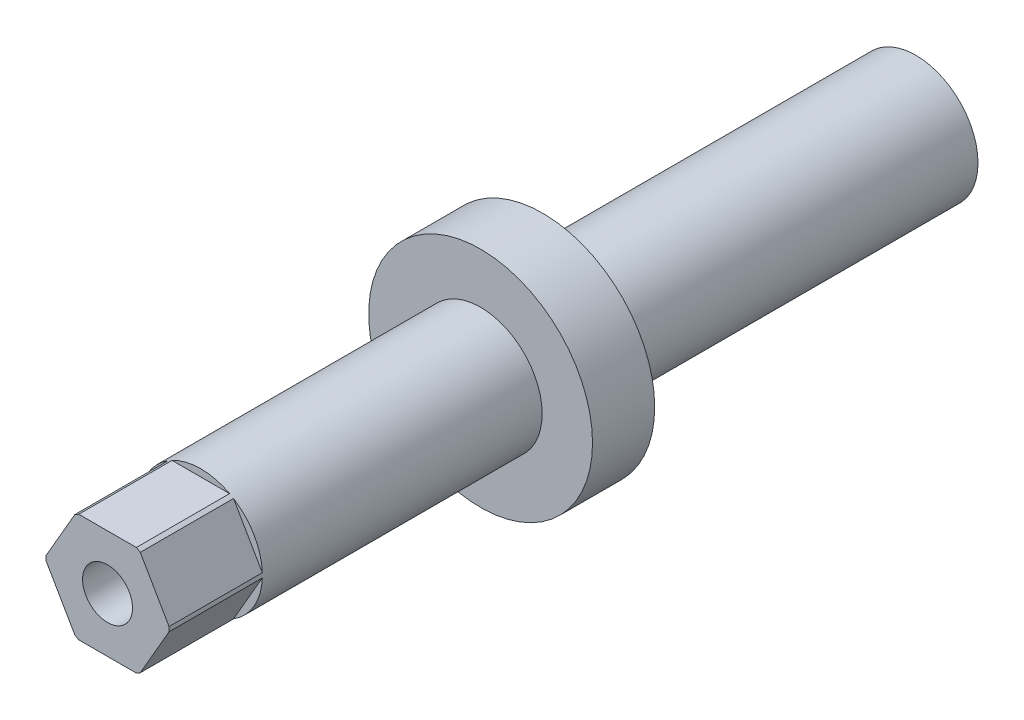
SolidWorks part; units mm, degrees
ref_plane "Front Plane" through (0, 0, 0) normal (0, 0, 1) x (1, 0, 0)
ref_plane "Top Plane" through (0, 0, 0) normal (0, 1, 0) x (1, 0, 0)
ref_plane "Right Plane" through (0, 0, 0) normal (1, 0, 0) x (0, 0, -1)
sketch "Sketch1" plane through (0, 0, 0) normal (1, 0, 0) x (0, 0, -1)
  line L0 (0, 6.2865) -> (0, -6.2865)
  line L1 (0, -6.2865) -> (38.1, -6.2865)
  line L2 (38.1, -6.2865) -> (38.1, -11.43)
  line L3 (38.1, -11.43) -> (44.45, -11.43)
  line L4 (44.45, -11.43) -> (44.45, -6.35)
  line L5 (44.45, -6.35) -> (82.55, -6.35)
  line L6 (82.55, -6.35) -> (82.55, 6.35)
  line L7 (82.55, 6.35) -> (44.45, 6.35)
  line L8 (44.45, 6.35) -> (44.45, 11.43)
  line L9 (44.45, 11.43) -> (38.1, 11.43)
  line L10 (38.1, 11.43) -> (38.1, 6.2865)
  line L11 (38.1, 6.2865) -> (0, 6.2865)
  line L12 (0, 0) -> (82.55, 0) construction
  point P5 (0, 0)
  dimension "D1" = 12.573
  dimension "D2" = 22.86
  dimension "D3" = 12.7
  dimension "D4" = 38.1
  dimension "D5" = 6.35
  dimension "D6" = 38.1
revolve "Revolve2" add sketch "Sketch1" angle 360 about L12 region at (0, 3.494, -41.3721)
hole_wizard "1/4-20 Tapped Hole1" positions "Sketch2" profile "Sketch3" tap size "1/4-20" standard "ANSI Inch" end condition through all
sketch "Sketch2" plane through (0, 0, -82.55) normal (0, 0, -1) x (-1, 0, 0)
  point P0 (0, 0)
cosmetic thread "Hole Thread1" parameters "D2"=6.35
sketch "Sketch3" plane through (0, 0, -82.55) normal (1, 0, 0) x (0, 1, 0)
  line L0 (0, 0) -> (0, 82.55)
  line L1 (0, 82.55) -> (2.5527, 82.55)
  line L2 (2.5527, 82.55) -> (2.5527, 0)
  line L5 (2.5527, 0) -> (0, 0)
  line L11 (0, -6.35) -> (0, 107.95) construction
  dimension "Thru Tap Drill Dia." = 5.1054
  dimension "Thru Tap Drill Depth" = 82.55
sketch "Sketch4" plane through (0, 0, 0) normal (0, 0, 1) x (1, 0, 0)
  line L1 (-6.4158, 0) -> (-3.2079, -5.5562)
  line L2 (-3.2079, -5.5562) -> (3.2079, -5.5562)
  line L3 (3.2079, -5.5562) -> (6.4158, 0)
  line L4 (6.4158, 0) -> (3.2079, 5.5563)
  line L5 (3.2079, 5.5563) -> (-3.2079, 5.5563)
  line L6 (-3.2079, 5.5563) -> (-6.4158, 0)
  circle A0 centre (0, 0) radius 5.5562 construction
  circle A2 centre (0, 0) radius 6.2865 construction
  circle A3 centre (0, 0) radius 6.2865
  circle M8 centre (0, 0) radius 6.2865
  dimension "D1" = 11.1125
extrude "Cut-Extrude1" cut sketch "Sketch4" against normal blind 9.525 contours L5 M8 | L4 M8 | L3 M8 | L2 M8 | L1 M8 | L6 M8 region at (-5.0661, -2.9249, 0) region at (-5.0661, 2.9249, 0) region at (0, -5.8499, 0) region at (0, 5.8499, 0) region at (5.0661, -2.9249, 0) region at (5.0661, 2.9249, 0)
